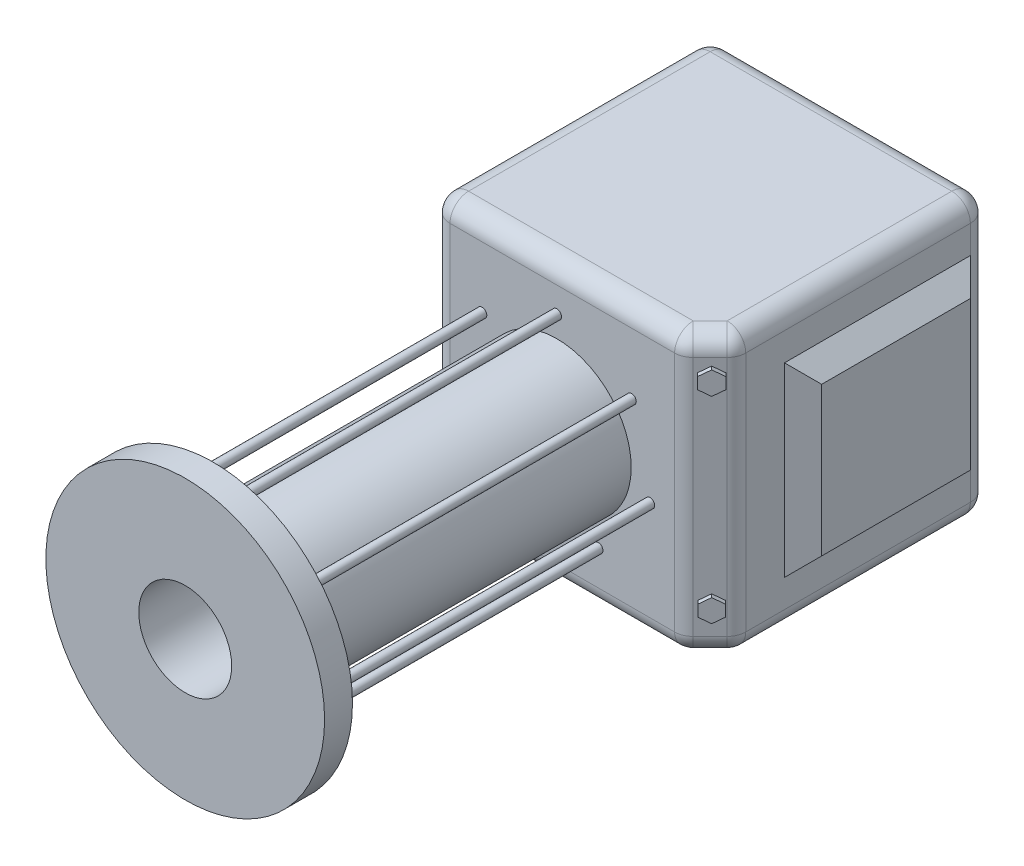
SolidWorks part; units mm, degrees
ref_plane "Front Plane" through (0, 0, 0) normal (0, 0, 1) x (1, 0, 0)
ref_plane "Top Plane" through (0, 0, 0) normal (0, 1, 0) x (1, 0, 0)
ref_plane "Right Plane" through (0, 0, 0) normal (1, 0, 0) x (0, 0, -1)
sketch "Sketch2" plane through (0, 0, 0) normal (1, 0, 0) x (0, 0, -1)
  line L1 (-15, -15) -> (15, -15)
  line L2 (-15, -15) -> (-15, 15)
  line L3 (-15, 15) -> (15, 15)
  line L4 (15, -15) -> (15, 15)
  line L5 (-15, -15) -> (15, 15) construction
  line L6 (-15, 15) -> (15, -15) construction
  point P0 (0, 0)
  dimension "D1" = 30
  dimension "D2" = 30
extrude "Boss-Extrude3" add sketch "Sketch2" along normal blind 30
sketch "Sketch4" plane through (0, 0, 0) normal (-1, 0, 0) x (0, 0, 1)
  circle A0 centre (0, 0) radius 5
  dimension "D1" = 10
chamfer "Chamfer1" distance 3 angle 45 1 edges at (30, 0, 15)
sketch "Sketch5" plane through (0, 0, 15) normal (0, 0, 1) x (1, 0, 0)
  circle A0 centre (13.5, 0) radius 8
  dimension "D1" = 16
extrude "Boss-Extrude5" add sketch "Sketch5" along normal blind 37
sketch "Sketch7" plane through (0, 0, 52) normal (0, 0, 1) x (1, 0, 0)
  circle A0 centre (13.5, 0) radius 15
extrude "Boss-Extrude6" add sketch "Sketch7" along normal blind 3
sketch "Sketch8" plane through (0, 0, 55) normal (0, 0, 1) x (1, 0, 0)
  circle A0 centre (13.5, 0) radius 5
  dimension "D1" = 10
extrude "Cut-Extrude1" cut sketch "Sketch8" against normal blind 10 contours A0
sketch "Sketch10" plane through (0, 0, 55) normal (0, 0, 1) x (1, 0, 0)
  line L0 (-1.5, 0) -> (13.5, 0)
  line L1 (13.5, 0) -> (13.5, 10.2883)
  circle A0 centre (13.5, 0) radius 15 construction
  circle A1 centre (13.5, 10.2883) radius 0.5
  dimension "D1" = 1
extrude "Boss-Extrude8" add sketch "Sketch10" against normal blind 47 contours A1 region at (13.8436, 9.9447, 55)
pattern_circular "CirPattern1" count 7 over 360 about axis through (13.5, 0, 55) along (0, 0, 1) of "Boss-Extrude8"
fillet "Fillet2" radius 2 1 edges at (30, 0, 12)
fillet "Fillet3" radius 2 7 edges at (28.2071, -15, 13.7929) (29.8478, -15, 11.9369) (28.2071, 15, 13.7929) (29.8478, 15, 11.9369) (30, 0, -15) (30, -15, -1.9142) (30, 15, -1.9142)
fillet "Fillet4" radius 2 12 edges at (26.1716, 14.4142, 15) (27, 0, 15) (26.1716, -14.4142, 15) (29.4142, -14.4142, -14.4142) (29.4142, 14.4142, -14.4142) (0, 15, 0) (12.0858, 15, 15) (0, -15, 0) (12.0858, -15, 15) (0, 0, -15) (14, -15, -15) (14, 15, -15)
sketch "Sketch12" plane through (21, 0, 21) normal (0.7071, 0, 0.7071) x (0.7071, 0, -0.7071)
  line L1 (10.7201, 12.1973) -> (9.6486, 11.5787)
  line L2 (9.6486, 11.5787) -> (9.6486, 10.3415)
  line L3 (9.6486, 10.3415) -> (10.7201, 9.7229)
  line L4 (10.7201, 9.7229) -> (11.7915, 10.3415)
  line L5 (11.7915, 10.3415) -> (11.7915, 11.5787)
  line L6 (11.7915, 11.5787) -> (10.7201, 12.1973)
  line L7 (10.7201, -9.0299) -> (9.6678, -9.6374)
  line L8 (9.6678, -9.6374) -> (9.6678, -10.8525)
  line L9 (9.6678, -10.8525) -> (10.7201, -11.46)
  line L10 (10.7201, -11.46) -> (11.7723, -10.8525)
  line L11 (11.7723, -10.8525) -> (11.7723, -9.6374)
  line L12 (11.7723, -9.6374) -> (10.7201, -9.0299)
  circle A0 centre (10.7201, 10.9601) radius 1.0715 construction
  circle A1 centre (10.7201, -10.245) radius 1.0523 construction
extrude "Boss-Extrude11" add sketch "Sketch12" along normal blind 0.5
ref_plane "Plane2" through (0, -13, 15) normal (0, -1, 0) x (-1, 0, 0)
fillet "Fillet5" radius 2 3 edges at (0.5858, 14.4142, 14.4142) (0.5858, -14.4142, 14.4142) (0, 0, 15)
sketch "Sketch14" plane through (30, 0, 0) normal (1, 0, 0) x (0, 0, -1)
  line L0 (13, 0) -> (13, 10)
  line L1 (13, -13) -> (13, 13) construction
  line L2 (13, 10) -> (-7, 10)
  line L3 (-7, 10) -> (-7, -10)
  line L4 (-7, -10) -> (13, -10)
  line L5 (13, -10) -> (13, 0)
extrude "Boss-Extrude13" add sketch "Sketch14" along normal blind 2
chamfer "Chamfer2" distance 2 angle 45 4 edges at (32, -10, -3) (32, 0, 7) (32, 10, -3) (32, 0, -13)
extrude "Cut-Extrude2" cut sketch "Sketch4" against normal blind 8 contours A0
